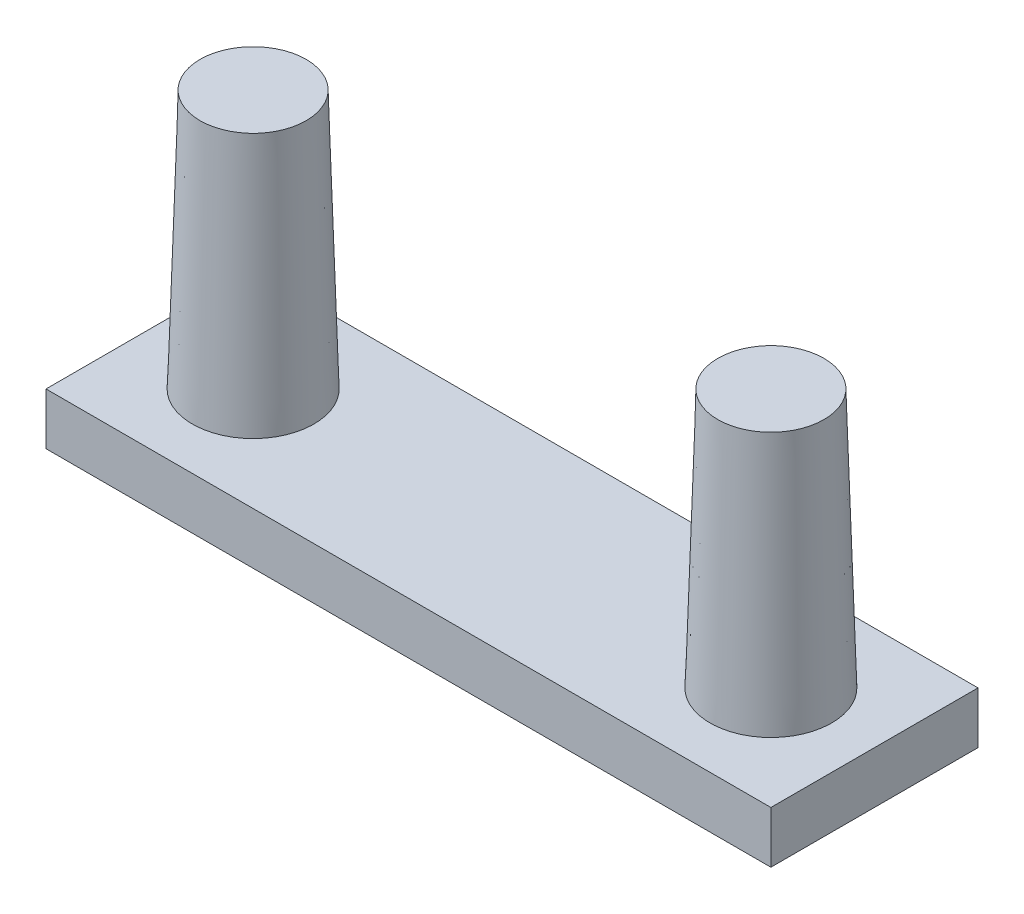
SolidWorks part; units mm, degrees
ref_plane "Front Plane" through (0, 0, 0) normal (0, 0, 1) x (1, 0, 0)
ref_plane "Top Plane" through (0, 0, 0) normal (0, 1, 0) x (1, 0, 0)
ref_plane "Right Plane" through (0, 0, 0) normal (1, 0, 0) x (0, 0, -1)
sketch "Sketch2" plane through (0, 0, 0) normal (0, 1, 0) x (1, 0, 0)
  line L1 (-14, -4) -> (14, -4)
  line L2 (-14, -4) -> (-14, 4)
  line L3 (-14, 4) -> (14, 4)
  line L4 (14, -4) -> (14, 4)
  line L5 (-14, -4) -> (14, 4) construction
  line L6 (-14, 4) -> (14, -4) construction
  point P0 (0, 0)
  dimension "D1" = 28
  dimension "D2" = 8
extrude "Boss-Extrude1" add sketch "Sketch2" along normal blind 2
sketch "Sketch3" plane through (0, 2, 0) normal (0, 1, 0) x (1, 0, 0)
  line L0 (0, 0) -> (10, 0)
  line L1 (0, 4) -> (0, -4) construction
  line L2 (14, 4) -> (-14, 4) construction
  line L3 (-14, -4) -> (14, -4) construction
  circle A0 centre (10, 0) radius 2.35
  dimension "D2" = 4.7
  dimension "D1" = 10
extrude "Boss-Extrude2" add sketch "Sketch3" along normal blind 10 contours A0 region at (10, 2, 2.2835)
chamfer "Chamfer1" distance 10 distance2 0.3 1 edges at (10, 12, 2.35) first distance on face at (10, 12, 2.35)
pattern_linear "LPattern1" count 2 spacing 20 along (-1, 0, 0) of "Boss-Extrude2", "Chamfer1"
